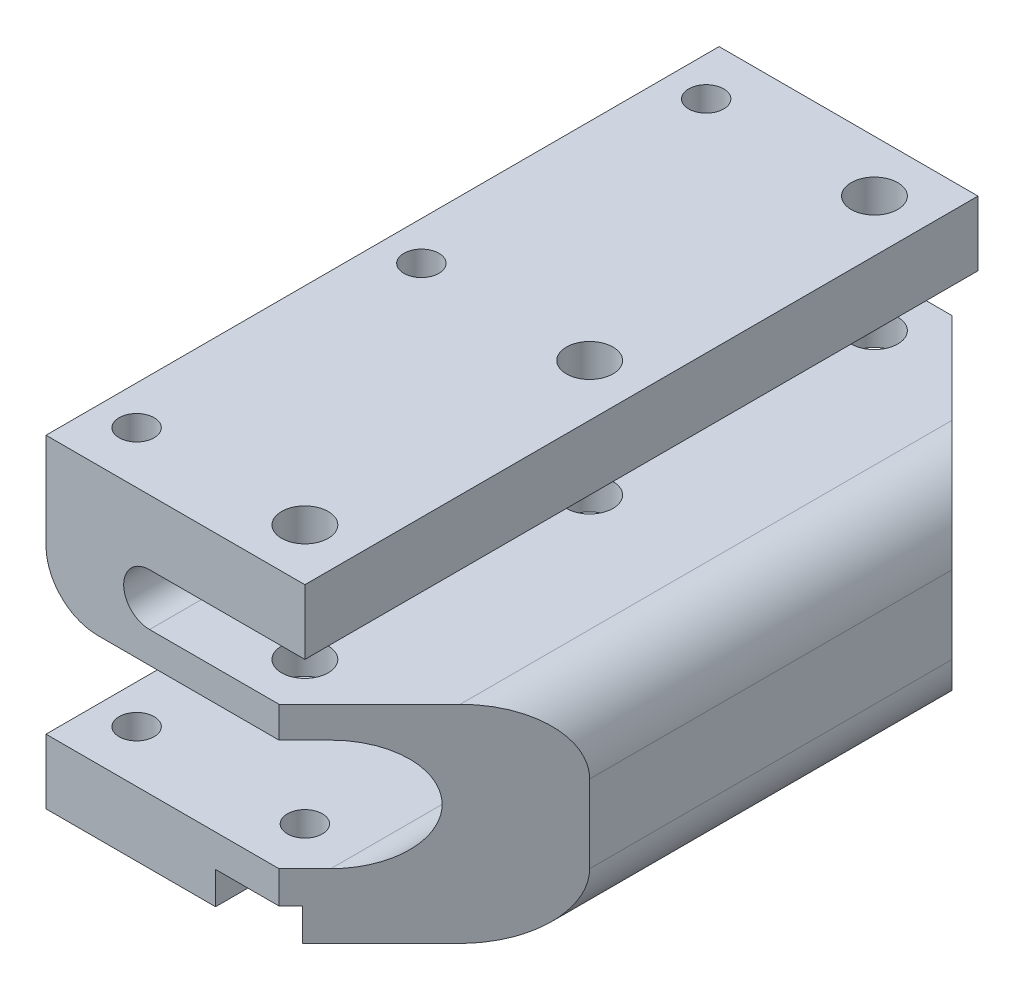
SolidWorks part; units mm, degrees
ref_plane "Front Plane" through (0, 0, 0) normal (0, 0, 1) x (1, 0, 0)
ref_plane "Top Plane" through (0, 0, 0) normal (0, 1, 0) x (1, 0, 0)
ref_plane "Right Plane" through (0, 0, 0) normal (1, 0, 0) x (0, 0, -1)
sketch "Sketch1" plane through (0, 0, 0) normal (0, 0, 1) x (1, 0, 0)
  line L1 (0, 0) -> (25, 0)
  line L2 (0, 0) -> (0, 5)
  line L3 (0, 5) -> (20, 5)
  line L4 (30, 5) -> (30, 11)
  line L6 (8, 20) -> (20, 20)
  line L7 (0, 25) -> (0, 17.6)
  line L8 (0, 25) -> (20, 25)
  line L9 (8, 16) -> (25, 16)
  line L12 (4, 13.6) -> (20, 13.6)
  line L14 (20, 25) -> (20, 20)
  arc A0 (8, 20) -> (8, 16) centre (8, 18) ccw
  arc A1 (0, 17.6) -> (4, 13.6) centre (4, 17.6) ccw
  arc A2 (30, 5) -> (25, 0) centre (25, 5) cw
  arc A3 (25, 16) -> (30, 11) centre (25, 11) cw
  arc A5 (20, 13.6) -> (20, 5) centre (20, 9.3) cw
  point P3 (7.9095, 0)
  point P12 (8, 4.5327)
  dimension "D4" = 5
  dimension "D5" = 2
  dimension "D1" = 20
  dimension "D8" = 4
  dimension "D9" = 5
  dimension "D11" = 8
  dimension "D12" = 5
  dimension "D2" = 5
  dimension "D3" = 25
  dimension "D6" = 2.4
  dimension "D7" = 30
  dimension "D10" = 10
extrude "Boss-Extrude1" add sketch "Sketch1" along normal blind 52
sketch "Sketch2" plane through (0, 25, 0) normal (0, 1, 0) x (1, 0, 0)
  line L0 (0, -26) -> (46.5982, -26) construction
  line L1 (0, -52) -> (0, 0) construction
  circle A0 centre (16, -26) radius 1.8
  dimension "D1" = 3.6
  dimension "D3" = 16
extrude "Cut-Extrude1" cut sketch "Sketch2" against normal up to surface (11.4 mm away) up to face at (12, 13.6, 26)
sketch "Sketch4" plane through (0, 25, 0) normal (0, 1, 0) x (1, 0, 0)
  line L0 (20, -26) -> (0, -26) construction
  line L1 (20, -52) -> (20, 0) construction
  line L2 (0, -52) -> (0, 0) construction
  circle A0 centre (3, -26) radius 1.35
  dimension "D2" = 2.7
  dimension "D1" = 3
extrude "Cut-Extrude3" cut sketch "Sketch4" against normal up to next
sketch "Sketch5" plane through (0, 0, 0) normal (0, -1, 0) x (1, 0, 0)
  circle A0 centre (3, 26) radius 1.35
  circle A1 centre (3, 26) radius 1.35 construction
extrude "Cut-Extrude4" cut sketch "Sketch5" against normal up to next
sketch "Sketch6" plane through (0, 5, 0) normal (0, 1, 0) x (1, 0, 0)
  circle A0 centre (16, -26) radius 1.35
  circle A1 centre (16, -26) radius 1.8 construction
  dimension "D1" = 2.7
extrude "Cut-Extrude5" cut sketch "Sketch6" against normal through all
chamfer "Chamfer2" [suppressed] distance 6 angle 60
chamfer "Chamfer3" distance 12 angle 45 2 edges at (30, 8, 0) (30, 8, 52) tangent propagation no
pattern_linear "LPattern3" count 2 spacing 22 along (0, 0, 1) count 2 spacing 22 along (0, 0, -1) of "Cut-Extrude1", "Cut-Extrude3", "Cut-Extrude4", "Cut-Extrude5"
sketch "Sketch7" plane through (0, 0, 0) normal (0, -1, 0) x (1, 0, 0)
  line L0 (16, 41) -> (16, 32) construction
  line L1 (16, 20) -> (16, 11) construction
  line L2 (13.1, 32) -> (18.9, 32)
  line L3 (13.1, 32) -> (13.1, 20)
  line L4 (13.1, 20) -> (18.9, 20)
  line L5 (18.9, 32) -> (18.9, 20)
  line L6 (13.1, 11) -> (18.9, 11)
  line L7 (13.1, 11) -> (13.1, -1.747)
  line L8 (13.1, -1.747) -> (18.9, -1.747)
  line L9 (18.9, 11) -> (18.9, -1.747)
  line L10 (13.1, 41) -> (18.9, 41)
  line L11 (13.1, 41) -> (13.1, 54.0585)
  line L12 (13.1, 54.0585) -> (18.9, 54.0585)
  line L13 (18.9, 41) -> (18.9, 54.0585)
  line L14 (13.1, 26) -> (18.9, 26) construction
  circle A0 centre (16, 26) radius 1.35 construction
  point P1 (16, 26)
  dimension "D1" = 5.8
  dimension "D2" = 12
  dimension "D3" = 9
extrude "Cut-Extrude6" cut sketch "Sketch7" against normal blind 2.5
chamfer "Chamfer4" distance 2.5 angle 45 4 edges at (16, 2.5, 41) (16, 2.5, 20) (16, 2.5, 32) (16, 2.5, 11)
